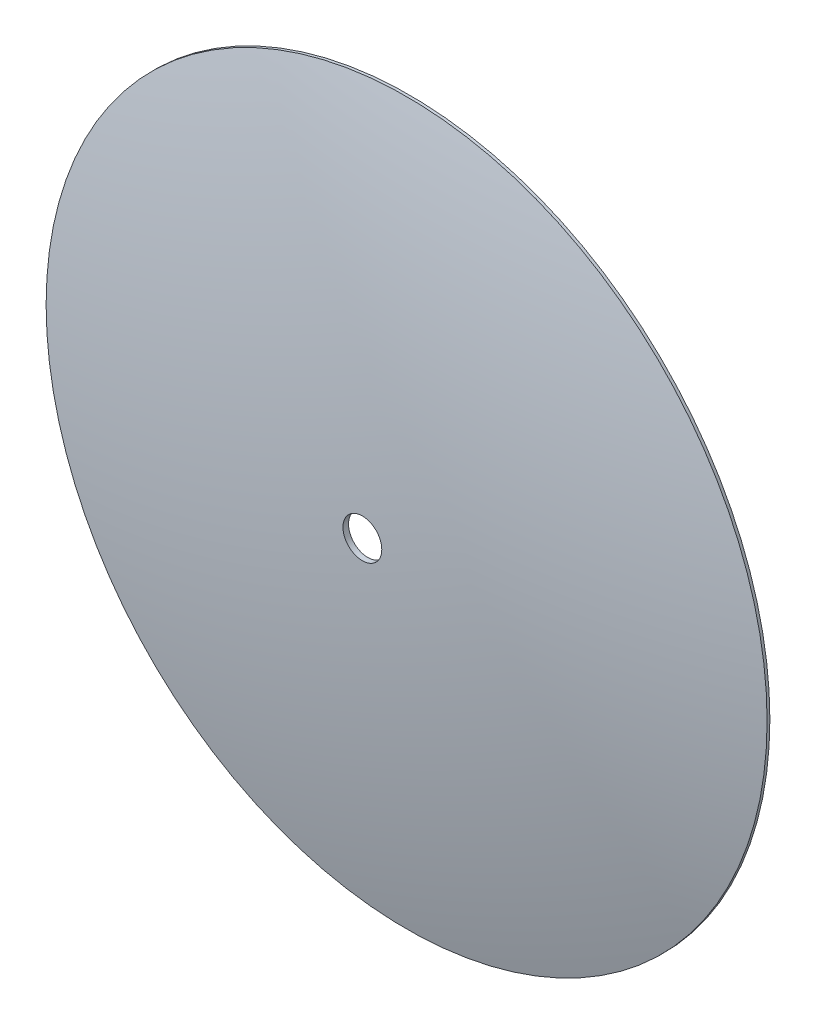
SolidWorks part; units mm, degrees
ref_plane "Front Plane" through (0, 0, 0) normal (0, 0, 1) x (1, 0, 0)
ref_plane "Top Plane" through (0, 0, 0) normal (0, 1, 0) x (1, 0, 0)
ref_plane "Right Plane" through (0, 0, 0) normal (1, 0, 0) x (0, 0, -1)
sketch "Sketch17" plane through (0, 0, 0) normal (0, 0, 1) x (1, 0, 0)
  circle A0 centre (0, 0) radius 165.1
  dimension "D1" = 330.2
extrude "Boss-Extrude1" add sketch "Sketch17" along normal blind 1.27
dome "Dome2" faces to dome 1 distance 20.32 reverse direction no elliptical dome no face at (165.1, 0, 1.27) parameters "D1"=20.32
shell "Shell2" thickness 2.54 removed face at (165.1, 0, 0)
sketch "Sketch18" plane through (0, 0, 0) normal (0, 0, 1) x (1, 0, 0)
  circle A0 centre (0, 0) radius 8.89
  dimension "D1" = 17.78
extrude "Cut-Extrude1" cut sketch "Sketch18" along normal up to next
